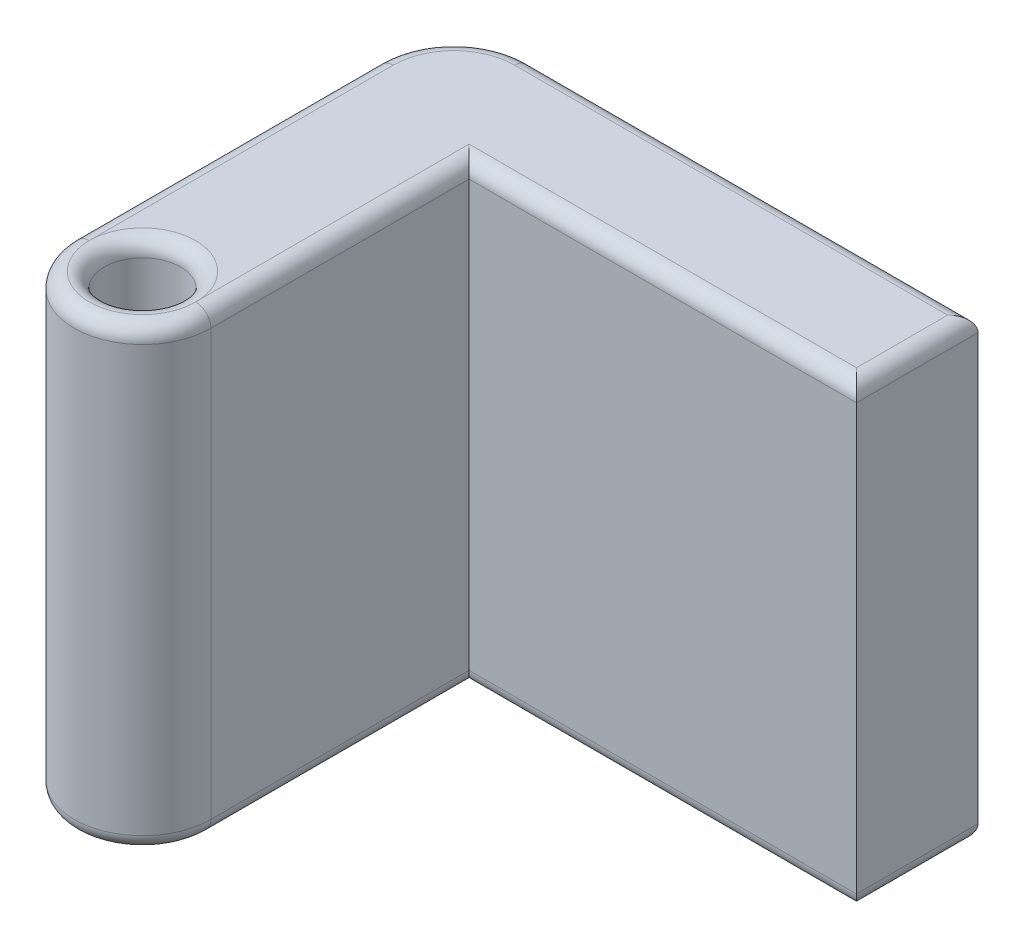
SolidWorks part; units mm, degrees
ref_plane "Front Plane" through (0, 0, 0) normal (0, 0, 1) x (1, 0, 0)
ref_plane "Top Plane" through (0, 0, 0) normal (0, 1, 0) x (1, 0, 0)
ref_plane "Right Plane" through (0, 0, 0) normal (1, 0, 0) x (0, 0, -1)
sketch "Sketch1" plane through (0, 0, 0) normal (0, 1, 0) x (1, 0, 0)
  line L0 (0, 0) -> (-34.5, 0)
  line L1 (-34.5, 0) -> (-34.5, -25)
  line L2 (-25.5, -25) -> (-25.5, -8)
  line L3 (-25.5, -8) -> (0, -8)
  line L4 (0, -8) -> (0, 0)
  arc A0 (-34.5, -25) -> (-25.5, -25) centre (-30, -25) ccw
  circle A1 centre (-30, -25) radius 2.5
  dimension "D2" = 5
  dimension "D1" = 25.5
  dimension "D3" = 9
  dimension "D4" = 8
  dimension "D5" = 17
extrude "Boss-Extrude1" add sketch "Sketch1" along normal blind 30
fillet "Fillet1" radius 1 14 edges at (-30, 0, 27.5) (-17.25, 0, 0) (-34.5, 0, 12.5) (-30, 0, 29.5) (-25.5, 0, 16.5) (-12.75, 0, 8) (0, 0, 4) (-30, 30, 27.5) (-12.75, 30, 8) (-25.5, 30, 16.5) (-30, 30, 29.5) (-34.5, 30, 12.5) (-17.25, 30, 0) (0, 30, 4)
fillet "Fillet2" radius 5 3 edges at (-34.2071, 0.2929, 0.2929) (-34.2071, 29.7071, 0.2929) (-34.5, 15, 0)
